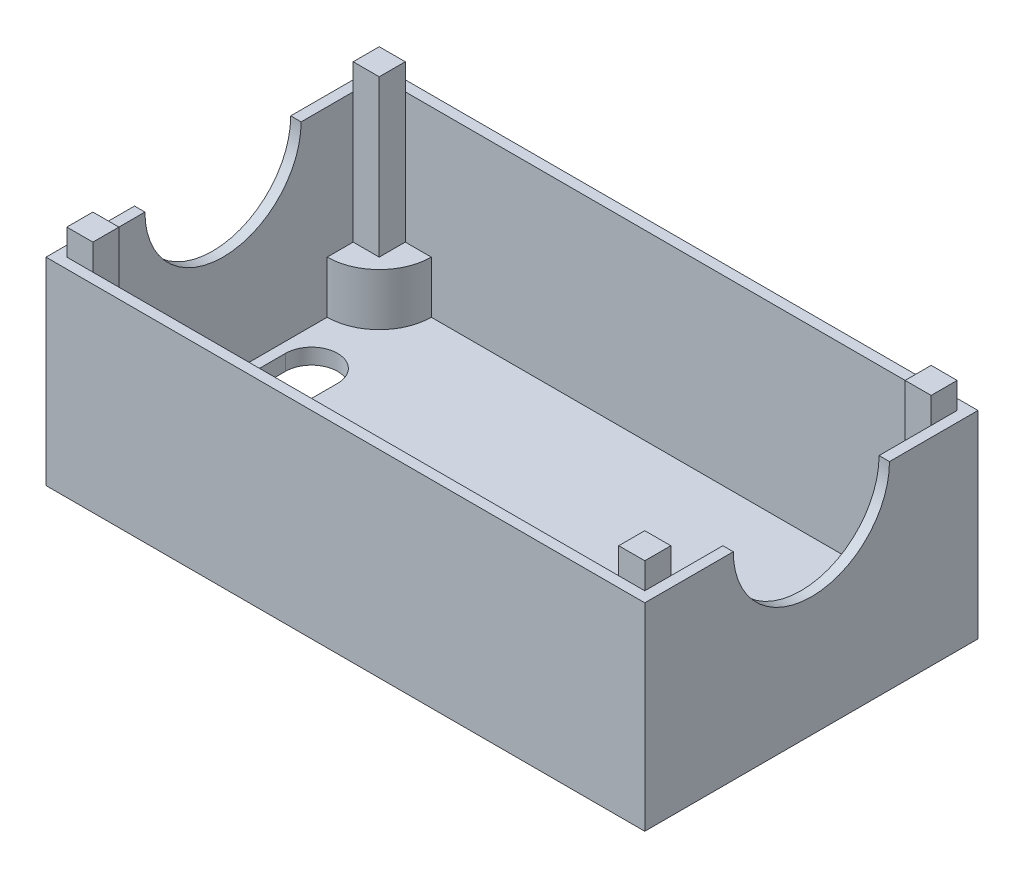
SolidWorks part; units mm, degrees
material "ABS"
ref_plane "Front Plane" through (0, 0, 0) normal (0, 0, 1) x (1, 0, 0)
ref_plane "Top Plane" through (0, 0, 0) normal (0, 1, 0) x (1, 0, 0)
ref_plane "Right Plane" through (0, 0, 0) normal (1, 0, 0) x (0, 0, -1)
sketch "Sketch1" plane through (0, 0, 0) normal (0, 1, 0) x (1, 0, 0)
  line L0 (-55, 0) -> (55, 0) construction
  line L1 (-57.5, 32) -> (57.5, 32)
  line L2 (-57.5, 32) -> (-57.5, -32)
  line L3 (-57.5, -32) -> (57.5, -32)
  line L4 (57.5, 32) -> (57.5, -32)
  line L5 (0, -55) -> (0, 55) construction
  dimension "D1" = 64
  dimension "D2" = 32
  dimension "D3" = 115
  dimension "D4" = 57.5
extrude "Boss-Extrude1" add sketch "Sketch1" along normal blind 3
sketch "Sketch2" plane through (0, 3, 0) normal (0, 1, 0) x (1, 0, 0)
  line L0 (57.5, 32) -> (-57.5, 32) construction
  line L1 (-55.5, -30) -> (55.5, -30)
  line L2 (-55.5, -30) -> (-55.5, 30)
  line L3 (-55.5, 30) -> (55.5, 30)
  line L4 (55.5, -30) -> (55.5, 30)
  line L5 (-55.5, -30) -> (55.5, 30) construction
  line L6 (-55.5, 30) -> (55.5, -30) construction
  line L7 (-57.5, 32) -> (-57.5, -32) construction
  line L9 (-57.5, 32) -> (57.5, 32)
  line L10 (-57.5, 32) -> (-57.5, -32)
  line L11 (-57.5, -32) -> (57.5, -32)
  line L12 (57.5, 32) -> (57.5, -32)
  point P0 (0, 0)
  dimension "D1" = 2
  dimension "D2" = 2
extrude "Boss-Extrude2" add sketch "Sketch2" along normal blind 35
sketch "Sketch12" plane through (0, 38, 0) normal (0, 1, 0) x (1, 0, 0)
  line L1 (-55.5, 30) -> (-50.5, 30)
  line L2 (-55.5, 30) -> (-55.5, 25)
  line L3 (-55.5, 25) -> (-50.5, 25)
  line L4 (-50.5, 30) -> (-50.5, 25)
  line L5 (0, 43.3275) -> (0, 0) construction
  line L6 (0, 0) -> (63.2414, 0) construction
  line L7 (50.5, 30) -> (50.5, 25)
  line L8 (55.5, 25) -> (50.5, 25)
  line L9 (55.5, 30) -> (55.5, 25)
  line L10 (55.5, 30) -> (50.5, 30)
  line L11 (55.5, -30) -> (55.5, -25)
  line L12 (55.5, -25) -> (50.5, -25)
  line L13 (55.5, -30) -> (50.5, -30)
  line L14 (50.5, -30) -> (50.5, -25)
  line L15 (-50.5, -30) -> (-50.5, -25)
  line L16 (-55.5, -25) -> (-50.5, -25)
  line L17 (-55.5, -30) -> (-55.5, -25)
  line L18 (-55.5, -30) -> (-50.5, -30)
  dimension "D1" = 5
  dimension "D2" = 5
extrude "Boss-Extrude9" add sketch "Sketch12" along normal blind 5 and the other way blind 37
sketch "Sketch14" plane through (0, 3, 0) normal (0, 1, 0) x (1, 0, 0)
  line L0 (-48.5, -10) -> (-48.5, 10) construction
  line L1 (-53.5, -10) -> (-53.5, 10)
  line L2 (-43.5, -10) -> (-43.5, 10)
  line L3 (-55, 0) -> (55, 0) construction
  line L4 (-55.5, 25) -> (-55.5, -25) construction
  arc A0 (-53.5, -10) -> (-43.5, -10) centre (-48.5, -10) ccw
  arc A1 (-43.5, 10) -> (-53.5, 10) centre (-48.5, 10) ccw
  point P2 (-48.5, 0)
  dimension "D3" = 5
  dimension "D1" = 0
  dimension "D2" = 2
  dimension "D4" = 20
extrude "Cut-Extrude6" cut sketch "Sketch14" against normal through all
sketch "Sketch17" plane through (0, 3, 0) normal (0, 1, 0) x (1, 0, 0)
  line L0 (0, 39.8656) -> (0, -43.9459) construction
  line L1 (-55.5, 30) -> (-45.5, 30)
  line L2 (-55.5, 30) -> (-55.5, 20)
  line L3 (-55.5, 20) -> (-45.5, 20)
  line L4 (-45.5, 30) -> (-45.5, 20)
  line L5 (-58.0064, 0) -> (59.7708, 0) construction
  line L6 (-55, 0) -> (55, 0) construction
  line L7 (55.5, 20) -> (45.5, 20)
  line L8 (55.5, 30) -> (55.5, 20)
  line L9 (55.5, 30) -> (45.5, 30)
  line L10 (45.5, 30) -> (45.5, 20)
  line L11 (55.5, -20) -> (45.5, -20)
  line L12 (55.5, -30) -> (45.5, -30)
  line L13 (45.5, -30) -> (45.5, -20)
  line L14 (-55.5, -30) -> (-55.5, -20)
  line L15 (-55.5, -30) -> (-45.5, -30)
  line L16 (-45.5, -30) -> (-45.5, -20)
  line L17 (-55.5, -20) -> (-45.5, -20)
  line M15 (55.5, -25) -> (55.5, 25)
  line M18 (50.5, 30) -> (-50.5, 30)
  line M21 (-55.5, 25) -> (-55.5, -25)
  line M24 (-50.5, -30) -> (50.5, -30)
  line M35 (-55.5, -25) -> (-50.5, -25)
  line M36 (-50.5, -25) -> (-50.5, -30)
  line M37 (50.5, -30) -> (50.5, -25)
  line M38 (50.5, -25) -> (55.5, -25)
  line M39 (55.5, 25) -> (50.5, 25)
  line M40 (50.5, 25) -> (50.5, 30)
  line M41 (-50.5, 30) -> (-50.5, 25)
  line M42 (-50.5, 25) -> (-55.5, 25)
  dimension "D1" = 10
  dimension "D2" = 10
extrude "Boss-Extrude11" add sketch "Sketch17" along normal blind 10 contours L4 L3 M18 M41 M42 M21 | L10 L7 M18 M15 M39 M40 | L13 L11 M24 M37 M38 M15 | L17 L16 M21 M35 M36 M24 region at (-49.6667, 3, -24.1667) region at (49.6667, 3, -24.1667) region at (-49.6667, 3, 24.1667) region at (49.6667, 3, 24.1667)
sketch "Sketch19" plane through (0, 0, 0) normal (0, -1, 0) x (1, 0, 0)
  line L0 (0, 39.645) -> (0, -39.8656) construction
  line L1 (-55.5, 30) -> (-50, 30)
  line L2 (-55.5, 30) -> (-55.5, 24.5)
  line L3 (-55.5, 24.5) -> (-50, 24.5)
  line L4 (-50, 30) -> (-50, 24.5)
  line L5 (-64.5128, 0) -> (62.6381, 0) construction
  line L6 (-57.5, 32) -> (57.5, 32) construction
  line L7 (-57.5, -32) -> (-57.5, 32) construction
  line L8 (50, 30) -> (50, 24.5)
  line L9 (55.5, 24.5) -> (50, 24.5)
  line L10 (55.5, 30) -> (55.5, 24.5)
  line L11 (55.5, 30) -> (50, 30)
  line L12 (55.5, -30) -> (55.5, -24.5)
  line L13 (55.5, -24.5) -> (50, -24.5)
  line L14 (50, -30) -> (50, -24.5)
  line L15 (55.5, -30) -> (50, -30)
  line L16 (-50, -30) -> (-50, -24.5)
  line L17 (-55.5, -24.5) -> (-50, -24.5)
  line L18 (-55.5, -30) -> (-55.5, -24.5)
  line L19 (-55.5, -30) -> (-50, -30)
  dimension "D1" = 2
  dimension "D2" = 2
  dimension "D3" = 5.5
  dimension "D4" = 5.5
extrude "Cut-Extrude7" cut sketch "Sketch19" against normal blind 7
fillet "Fillet2" radius 10 4 edges at (-45.5, 8, 20) (45.5, 8, -20) (45.5, 8, 20) (-45.5, 8, -20)
sketch "Sketch20" plane through (-57.5, 0, 0) normal (-1, 0, 0) x (0, 0, 1)
  line L0 (-32, 38) -> (32, 38) construction
  circle A0 centre (0, 38) radius 15
  dimension "D1" = 30
extrude "Cut-Extrude8" cut sketch "Sketch20" against normal through all
